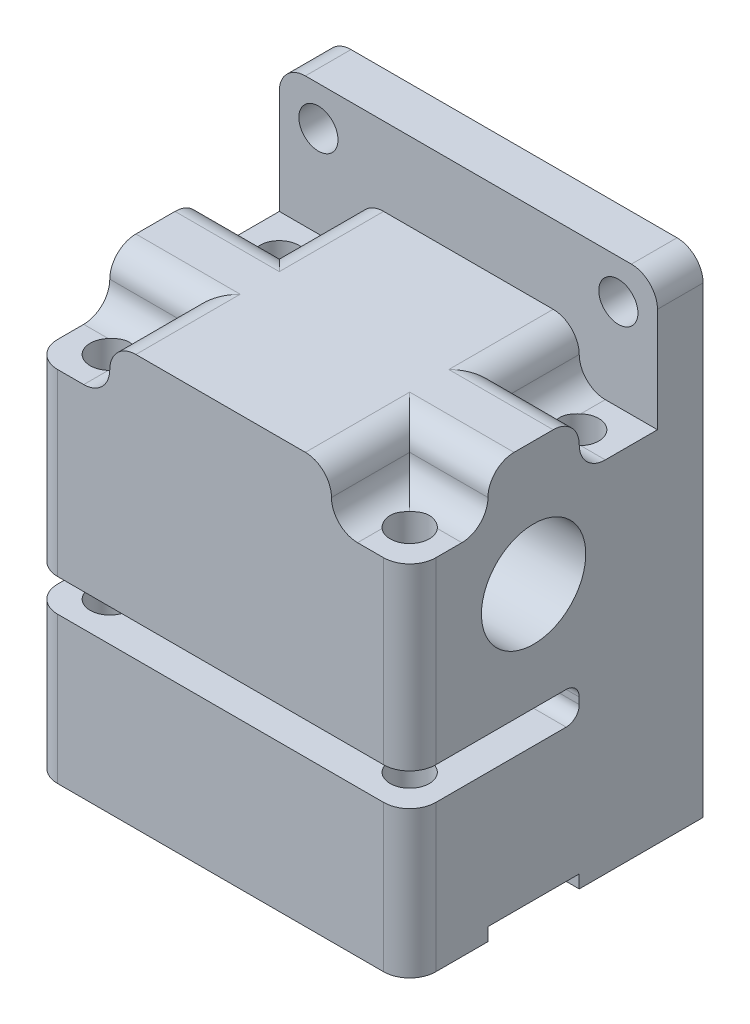
SolidWorks part; units mm, degrees
ref_plane "Front Plane" through (0, 0, 0) normal (0, 0, 1) x (1, 0, 0)
ref_plane "Top Plane" through (0, 0, 0) normal (0, 1, 0) x (1, 0, 0)
ref_plane "Right Plane" through (0, 0, 0) normal (1, 0, 0) x (0, 0, -1)
sketch "Sketch1" plane through (0, 0, 0) normal (0, 0, 1) x (1, 0, 0)
  line L0 (0, 0) -> (29, 0)
  line L1 (29, 0) -> (29, -37.5)
  line L2 (29, -37.5) -> (0, -37.5)
  line L3 (0, -37.5) -> (0, 0)
  dimension "D1" = 29
  dimension "D2" = 37.5
extrude "Boss-Extrude1" add sketch "Sketch1" along normal blind 3.5
sketch "Sketch2" plane through (0, 0, 3.5) normal (0, 0, 1) x (1, 0, 0)
  line L0 (0, -37.5) -> (29, -37.5)
  line L1 (29, -37.5) -> (29, -6)
  line L2 (29, -37.5) -> (29, 0) construction
  line L3 (29, -6) -> (0, -6)
  line L4 (0, 0) -> (0, -37.5) construction
  line L5 (0, -6) -> (0, -37.5)
  dimension "D1" = 31.5
extrude "Boss-Extrude2" add sketch "Sketch2" along normal blind 19
sketch "Sketch3" plane through (29, 0, 0) normal (1, 0, 0) x (0, 0, -1)
  line L0 (-3.5, -6) -> (-3.5, -37.5) construction
  line L1 (-22.5, -37.5) -> (0, -37.5) construction
  line L2 (-22.5, -6) -> (-22.5, -26.25) construction
  line L3 (-22.5, -37.5) -> (-22.5, -6) construction
  line L4 (-13, -6) -> (-13, -11.5) construction
  line L5 (-22.5, -6) -> (-3.5, -6) construction
  line L6 (-13, -11.5) -> (-13, -19.5) construction
  line L7 (-13, -37.5) -> (-16.5, -37.5)
  line L8 (-16.5, -37.5) -> (-16.5, -36.5)
  line L9 (-16.5, -36.5) -> (-9.5, -36.5)
  line L10 (-9.5, -36.5) -> (-9.5, -37.5)
  line L11 (-9.5, -37.5) -> (-13, -37.5)
  line L12 (-13, -19.5) -> (-13, -25) construction
  line L13 (-13, -25) -> (-13, -37) construction
  line L14 (-14.75, -37.5) -> (-14.75, -37) construction
  line L15 (-14.75, -37) -> (-14.75, -36.5) construction
  line L16 (-14.75, -37) -> (-13, -37) construction
  line L17 (-13, -37) -> (-13, -37.5) construction
  line L18 (-13, -25) -> (-22.5, -25) construction
  line L19 (-22.5, -23.75) -> (-22.5, -25)
  line L20 (-22.5, -25) -> (-22.5, -26.25)
  line L21 (-22.5, -23.75) -> (-9.5, -23.75)
  line L22 (-9.5, -23.75) -> (-9.5, -26.25)
  line L23 (-9.5, -26.25) -> (-22.5, -26.25)
  circle A0 centre (-13, -15.5) radius 4
  dimension "D1" = 8
  dimension "D2" = 7
  dimension "D3" = 1
  dimension "D4" = 12
  dimension "D5" = 2.5
extrude "Cut-Extrude1" cut sketch "Sketch3" against normal up to surface (29 mm away) up to face at (0, -14.5, 8.6667)
sketch "Sketch4" plane through (0, 0, 9.5) normal (0, 0, 1) x (1, 0, 0)
  line L0 (0.6, -35.9) -> (1.6, -35.9)
  line L2 (1.6, -35.9) -> (1.6, -37.5) construction
  line L3 (0, -37.5) -> (29, -37.5) construction
  line L4 (1.6, -37.5) -> (1.9, -37.5)
  line L5 (1.9, -37.5) -> (2.6, -35.9)
  line L6 (0.6, -35.9) -> (1.3, -37.5)
  line L7 (1.3, -37.5) -> (1.6, -37.5)
  line L8 (1.6, -35.9) -> (2.6, -35.9)
  line L9 (0.6, -35.9) -> (0, -35.9) construction
  line L10 (0, -6) -> (0, -23.75) construction
  dimension "D1" = 1.6
  dimension "D2" = 2
  dimension "D3" = 0.6
  dimension "D4" = 0.6
extrude "Boss-Extrude3" add sketch "Sketch4" along normal up to surface (7 mm away) up to face at (14.5, -37, 16.5)
pattern_linear "LPattern2" count 14 spacing 2 along (1, 0, 0) of "Boss-Extrude3"
sketch "Sketch5" plane through (0, -6, 0) normal (0, 1, 0) x (1, 0, 0)
  line L0 (0, -3.5) -> (6, -9.5) construction
  line L1 (6, -9.5) -> (6, -3.5) construction
  line L2 (29, -3.5) -> (0, -3.5) construction
  line L3 (6, -9.5) -> (0, -9.5) construction
  line L4 (0, -22.5) -> (0, -3.5) construction
  line L5 (29, -3.5) -> (23, -9.5) construction
  line L6 (23, -9.5) -> (29, -9.5) construction
  line L7 (29, -22.5) -> (29, -3.5) construction
  line L8 (23, -3.5) -> (23, -9.5) construction
  line L10 (23, -16.5) -> (29, -16.5) construction
  line L11 (23, -16.5) -> (23, -22.5) construction
  line L12 (29, -22.5) -> (0, -22.5) construction
  line L13 (23, -22.5) -> (6, -22.5) construction
  line L14 (6, -22.5) -> (6, -16.5) construction
  line L15 (6, -16.5) -> (0, -16.5) construction
  line L16 (0, -22.5) -> (6, -16.5) construction
  line L18 (23, -16.5) -> (29, -22.5) construction
  circle A0 centre (3, -6.5) radius 1.5
  circle A1 centre (26, -6.5) radius 1.5
  circle A2 centre (26, -19.5) radius 1.5
  circle A3 centre (3, -19.5) radius 1.5
  dimension "D2" = 3
  dimension "D1" = 6
extrude "Cut-Extrude2" cut sketch "Sketch5" against normal up to surface (31.5 mm away) up to face at (14.5333, -37.5, 12.4167)
sketch "Sketch6" plane through (0, 0, 3.5) normal (0, 0, 1) x (1, 0, 0)
  line L0 (0, 0) -> (0, -6) construction
  line L1 (0, 0) -> (0, -6) construction
  line L2 (0, -6) -> (6, 0) construction
  line L3 (29, 0) -> (0, 0) construction
  line L4 (6, 0) -> (0, 0) construction
  line L5 (29, 0) -> (29, -6) construction
  line L6 (29, -6) -> (29, 0) construction
  line L7 (29, -6) -> (23, 0) construction
  line L8 (23, 0) -> (29, 0) construction
  circle A0 centre (3, -3) radius 1.5
  circle A1 centre (26, -3) radius 1.5
  dimension "D2" = 3
  dimension "D1" = 6
extrude "Cut-Extrude3" cut sketch "Sketch6" against normal up to surface (3.5 mm away) up to face at (14.5, -18.75, 0)
sketch "Sketch7" plane through (0, -6, 0) normal (0, 1, 0) x (1, 0, 0)
  line L0 (0, -3.5) -> (0, -9.5)
  line L1 (0, -22.5) -> (0, -3.5) construction
  line L2 (0, -9.5) -> (6, -9.5)
  line L3 (6, -9.5) -> (6, -3.5)
  line L4 (29, -3.5) -> (0, -3.5) construction
  line L5 (6, -3.5) -> (0, -3.5)
  line L6 (29, -3.5) -> (23, -3.5)
  line L7 (23, -3.5) -> (23, -9.5)
  line L8 (23, -9.5) -> (29, -9.5)
  line L9 (29, -22.5) -> (29, -3.5) construction
  line L10 (29, -9.5) -> (29, -3.5)
  line L11 (0, -22.5) -> (0, -16.5)
  line L12 (0, -16.5) -> (6, -16.5)
  line L13 (6, -16.5) -> (6, -22.5)
  line L14 (29, -22.5) -> (0, -22.5) construction
  line L15 (6, -22.5) -> (0, -22.5)
  line L16 (29, -22.5) -> (29, -16.5)
  line L17 (29, -16.5) -> (23, -16.5)
  line L18 (23, -16.5) -> (23, -22.5)
  line L19 (23, -22.5) -> (29, -22.5)
  dimension "D1" = 6
extrude "Cut-Extrude5" cut sketch "Sketch7" against normal blind 4
fillet "Fillet2" radius 2 22 edges at (29, 0, 1.75) (0, 0, 1.75) (6, -6, 19.5) (6, -10, 19.5) (3, -10, 16.5) (3, -6, 16.5) (23, -6, 19.5) (23, -10, 19.5) (26, -10, 16.5) (26, -6, 16.5) (26, -10, 9.5) (26, -6, 9.5) (23, -6, 6.5) (23, -10, 6.5) (3, -6, 9.5) (3, -10, 9.5) (6, -6, 6.5) (6, -10, 6.5) (29, -16.875, 22.5) (29, -31.875, 22.5) (0, -31.875, 22.5) (0, -16.875, 22.5)
fillet "Fillet3" radius 1 2 edges at (14.5, -23.75, 9.5) (14.5, -26.25, 9.5)
equation "\"board_length\"= 260mm"
equation "\"board_height\"= 200mm"
equation "\"board_width\"= 16.5mm"
equation "\"token_thickness\"= 7mm"
equation "\"token_diameter\"= 32mm"
equation "\"board_side_lower_height\"= 55mm"
equation "\"board_side_height\"= 156.5mm"
equation "\"board_side_length\"= 100mm"
equation "\"board_slot_width\"= \"board_length\" / 7"
equation "\"token_ridge\"= ( \"token_thickness\" - 4mm ) / 2"
equation "\"token_ridge_width\"= 1.5mm"
equation "\"25T_outer_diameter\"= 20mm"
equation "\"25T_inner_diameter\"= 9mm"
equation "\"2T_screw_distance\"= 14mm"
equation "\"2T_outer_thickness\"= 2mm"
equation "\"2T_inner_thickness\"= 4.5mm"
equation "\"MG996R_outer_length\"= 54mm"
equation "\"MG996R_inner_length\"= 40mm"
equation "\"MG996R_width\"= 20mm"
equation "\"MG996R_height\"= 26.6mm"
equation "\"MG996R_full_height\"= 45.7mm"
equation "\"MG996R_full_width\"= 55.5mm"
equation "\"MG996R_screw_distance\"= 10mm"
equation "\"magnet_diameter\"= 10mm"
equation "\"magnet_thickness\"= 2mm"
equation "\"dispenser_barrel_margin\"= 2.5mm"
equation "\"dispenser_wheel_width\"= \"token_thickness\" + 5mm"
equation "\"dispenser_cover_margin\"= 3.0mm"
equation "\"dispenser_cover_thickness\"= 5.0mm"
equation "\"MG996R_major_axis_distance\"= 34.3mm"
equation "\"MG996R_major_screw_distance\"= 48.6mm"
equation "\"MG996R_minor_screw_distance\"= 9.9mm"
equation "\"MG996R_mid_height\"= 37.5mm"
equation "\"dispenser_slope\"= 30deg"
equation "\"dispenser_cover_length\"= 16mm"
equation "\"dispenser_carrier_width\"= 3.5mm"
equation "\"dispenser_carrier_height\"= 50mm"
equation "\"carrier_width\"= \"shaft_diameter\" * 2"
equation "\"shaft_diameter\"= 8mm"
equation "\"carrier_thickness\"=16mm"
equation "\"GT2_width\"= 7mm"
equation "\"GT2_outer_diameter\"= 18mm"
equation "\"GT2_inner_diameter\"= 12mm"
equation "\"GT2_pitch_diameter\"= 2mm"
equation "\"GT2_tooth_height\"= 1.6mm"
equation "\"GT2_upper_length\"= 0.6mm"
equation "\"belt_holder_width\"= \"GT2_width\" + 2 * 6mm"
equation "\"carrier_screw_distance\"= \"dispenser_cover_thickness\" + 3 * 6mm"
equation "\"D1@Sketch1\"=\"carrier_screw_distance\"+6mm"
equation "\"D2@Sketch1\"=\"carrier_height_bot\""
equation "\"D1@Boss-Extrude1\"=\"dispenser_carrier_width\""
equation "\"D1@Sketch2\"=\"carrier_width\"+\"GT2_inner_diameter\"+1mm+2.5mm"
equation "\"D1@Boss-Extrude2\"=\"GT2_width\"+2*6mm"
equation "\"D1@Sketch3\"=\"shaft_diameter\""
equation "\"D2@Sketch3\"=\"GT2_width\""
equation "\"D3@Sketch3\"=\"GT2_pitch_diameter\"/2"
equation "\"D1@Sketch4\"=\"GT2_tooth_height\""
equation "\"D2@Sketch4\"=\"GT2_pitch_diameter\""
equation "\"D3@Sketch4\"=\"GT2_upper_length\""
equation "\"D4@Sketch4\"=\"GT2_pitch_diameter\"*0.3"
equation "\"magnetometer_offset\"= 6mm"
equation "\"magnetometer_width\"= 15mm"
equation "\"magnetometer_length\"= 19mm"
equation "\"magnetometer_thickness\" = 2.5mm"
equation "\"timing_belt_gap\"= 2.5mm"
equation "\"carrier_height_top\"= 6mm + \"carrier_thickness\" + 0.5mm"
equation "\"carrier_height_bot\"= 6mm + \"carrier_thickness\" + \"GT2_inner_diameter\" + 1.0mm + \"timing_belt_gap\""
equation "\"D4@Sketch3\"=\"GT2_inner_diameter\""
equation "\"D5@Sketch3\"=\"magnetometer_thickness\""
